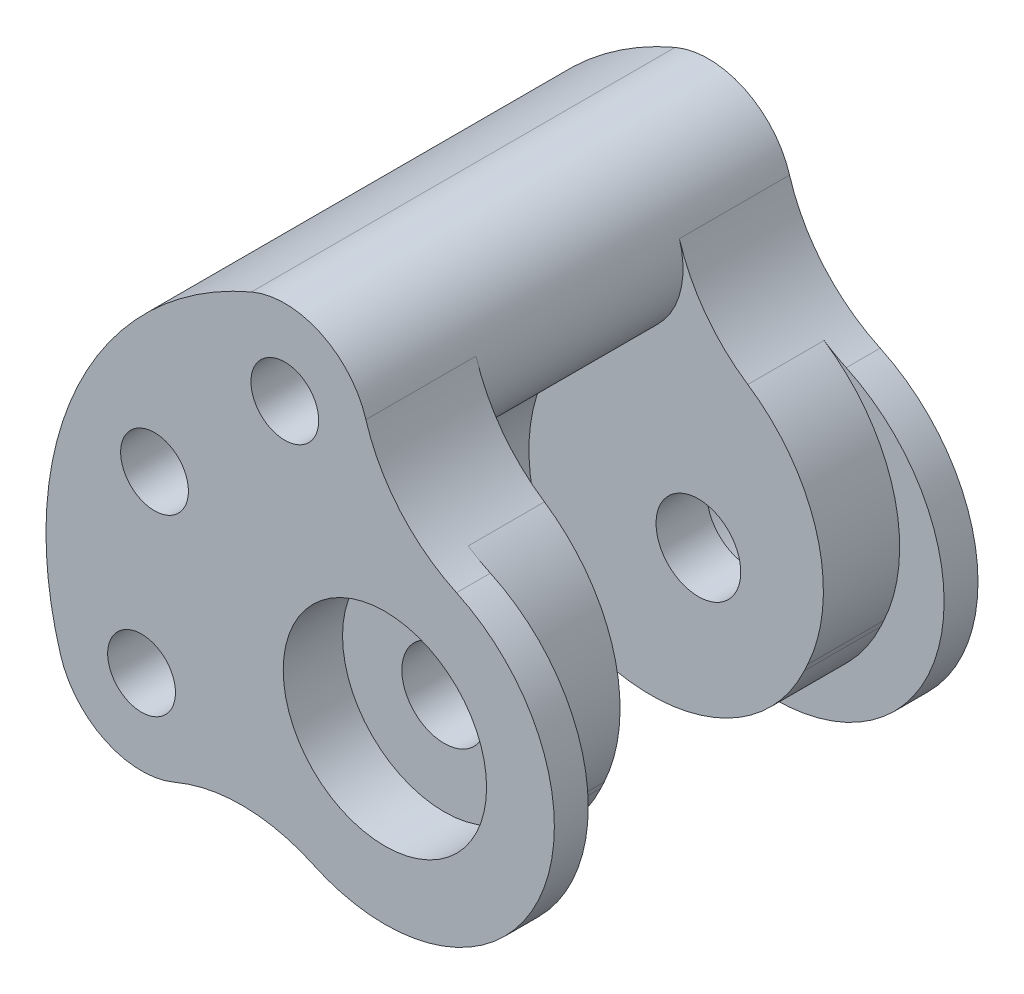
SolidWorks part; units mm, degrees
ref_plane "前视基准面" through (0, 0, 0) normal (0, 0, 1) x (1, 0, 0)
ref_plane "上视基准面" through (0, 0, 0) normal (0, 1, 0) x (1, 0, 0)
ref_plane "右视基准面" through (0, 0, 0) normal (1, 0, 0) x (0, 0, -1)
sketch "草图1" plane through (0, 0, 0) normal (0, 0, 1) x (1, 0, 0)
  line L0 (0, 0) -> (-18.1262, 8.4524) construction
  line L1 (-1000, 0) -> (49000, 0) construction
  line L2 (-0.1122, -0.2406) -> (-21131.0253, -45315.63) construction
  circle A0 centre (0, 0) radius 2.5
  circle A1 centre (0, 0) radius 20
  circle A2 centre (-13.5946, 6.3393) radius 2
  circle A3 centre (0, 0) radius 15 construction
  circle A4 centre (-5.9066, 13.7881) radius 2
  circle A5 centre (-14.359, -4.3381) radius 2
  circle A6 centre (-12.6785, -27.1892) radius 16.1484
  circle A7 centre (12.6785, 27.1892) radius 16.1484
  arc A8 (-19.1453, -5.7841) -> (-9.5727, -2.892) centre (-14.359, -4.3381) ccw
  arc A9 (-3.9378, 9.1921) -> (-7.8755, 18.3841) centre (-5.9066, 13.7881) ccw
  arc A12 (-9.5727, -2.892) -> (-3.9378, 9.1921) centre (0, 0) ccw
  point P18 (1.7431, -19.9239)
  point P19 (-16.383, -11.4715)
  dimension "D1" = 5
  dimension "D2" = 40
  dimension "D4" = 4
  dimension "D5" = 30
  dimension "D6" = 4
  dimension "D7" = 4
  dimension "D8" = 10
  dimension "D9" = 10
  dimension "D10" = 20
  dimension "D3" = 25
  dimension "D11" = 30
extrude "凸台-拉伸1" add sketch "草图1" along normal blind 25 contours A8 A12 A9 A1 A5 A4 A2 A0 region at (-5.5734, 2.5989, 0)
sketch "草图2" plane through (0, 0, 0) normal (0, 0, -1) x (-1, 0, 0)
  circle A0 centre (0, 0) radius 10
extrude "切除-拉伸1" cut sketch "草图2" against normal blind 12 from offset 6.5 offset against normal yes
fillet "圆角1" radius 10 4 edges at (-9.5727, -2.892, 21.75) (-3.9378, 9.1921, 21.75) (-3.9378, 9.1921, 3.25) (-9.5727, -2.892, 3.25)
sketch "草图3" plane through (0, 0, 0) normal (0, 0, -1) x (-1, 0, 0)
  circle A0 centre (0, 0) radius 6
  dimension "D1" = 12
extrude "切除-拉伸2" cut sketch "草图3" against normal blind 3.5
extrude "切除-拉伸3" cut sketch "草图3<2>" along normal blind 3.5 from surface starting at face at (-12.359, -4.3381, 25)
sketch "草图3<2>" plane through (0, 0, 0) normal (0, 0, -1) x (-1, 0, 0) same geometry as "草图3"
sketch "草图4" plane through (0, 0, 0) normal (0, 0, -1) x (-1, 0, 0)
  line L0 (-9.3623, 3.514) -> (-3.3261, -9.4307)
  line L1 (0, 0) -> (13.5946, 6.3393) construction
  arc A0 (-4.2262, 9.0631) -> (4.2262, -9.0631) centre (0, 0) ccw construction
  arc A1 (-9.3623, 3.514) -> (-3.3261, -9.4307) centre (0, 0) ccw
  dimension "D1" = 7
extrude "切除-拉伸4" cut sketch "草图4" against normal blind 21 from offset 2 offset against normal yes
fillet "圆角2" radius 10 4 edges at (3.3261, -9.4307, 20.75) (9.3623, 3.514, 20.75) (3.3261, -9.4307, 4.25) (9.3623, 3.514, 4.25)
